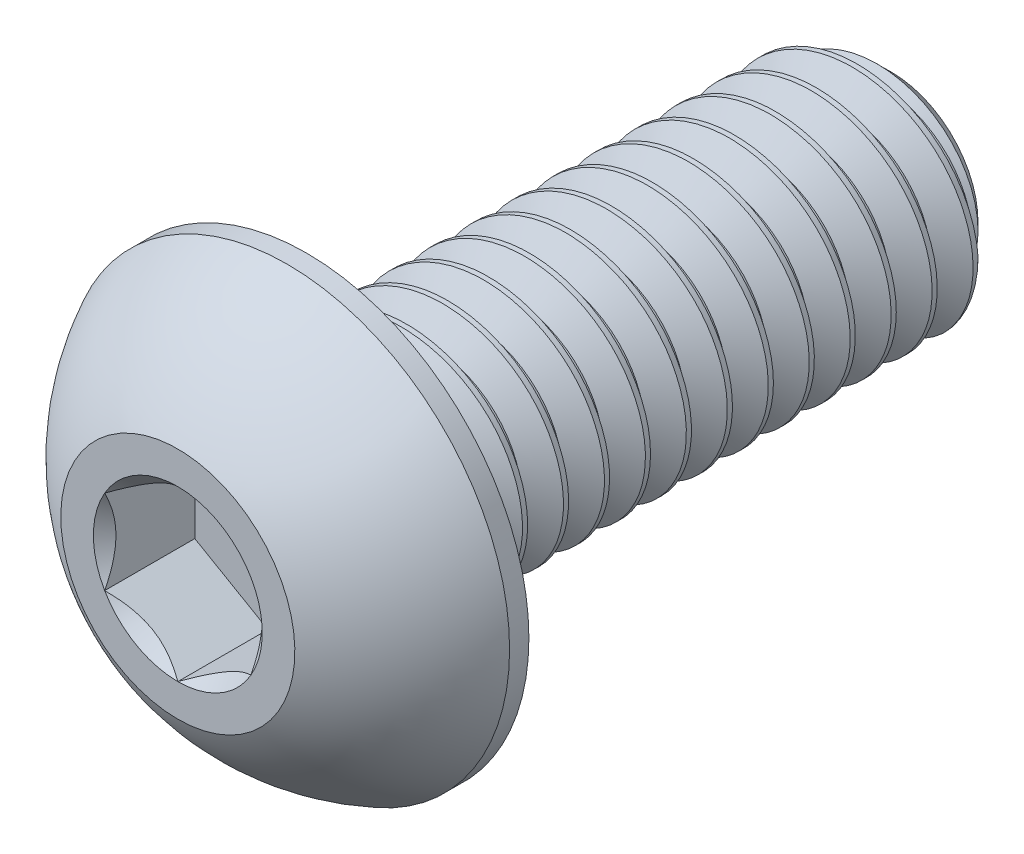
SolidWorks part; units mm, degrees
ref_plane "Front" through (0, 0, 0) normal (0, 0, 1) x (1, 0, 0)
ref_plane "Top" through (0, 0, 0) normal (0, 1, 0) x (1, 0, 0)
ref_plane "Right" through (0, 0, 0) normal (1, 0, 0) x (0, 0, -1)
sketch "Sketch1" plane through (0, 0, 0) normal (1, 0, 0) x (0, 0, -1)
  line L2 (2.2, 2) -> (12.2, 2)
  line L3 (12.2, 2) -> (12.2, 0)
  line L4 (12.2, 0) -> (2.2, 0)
  line L6 (1.87, 3.8) -> (2.2, 3.8) construction
  line L7 (12.2, 2) -> (12.2, -2) construction
  line L8 (0, 0) -> (2.2, 0) construction
  line L9 (2.2, 3.8) -> (2.2, -3.8) construction
  line L11 (2.2, 2) -> (2.2, 0)
  line L13 (0, 1.25) -> (0, -1.25) construction
  line L14 (0, 1.25) -> (0, 2) construction
  arc A3 (0, 2) -> (1.87, 3.8) centre (3.7264, 0) cw construction
  dimension "D1" = 0.33
revolve "Revolve1" add sketch "Sketch1" angle 360 mid plane about L4
sketch "Sketch3" plane through (0, 0, -12.2) normal (0, 0, -1) x (-1, 0, 0)
  circle A0 centre (0, 0) radius 2
curve "Helix/Spiral1" pitch 0.7 height 10.7 radius 2 centre (0, 0, -12.2) axis (0, 0, 1) start towards (0, 1, 0)
sketch "Sketch2" plane through (0, 0, 0) normal (1, 0, 0) x (0, 0, -1)
  line L0 (12.2, 2) -> (12.8125, 2)
  line L1 (12.8125, 2) -> (12.55, 1.5453)
  line L2 (12.55, 1.5453) -> (12.4625, 1.5453)
  line L3 (12.4625, 1.5453) -> (12.2, 2)
  line L4 (12.3312, 1.7727) -> (12.6812, 1.7727) construction
  dimension "D1" = 60
  dimension "D2" = 0.0875
  dimension "D3" = 0.35
chamfer "Chamfer1" distance 0.525 angle 45 1 edges at (0, 2, -12.2)
sweep "Cut-Sweep1" cut profiles "Sketch2" path "Helix/Spiral1" align with end faces yes
sketch "Sketch7" plane through (0, 0, 0) normal (1, 0, 0) x (0, 0, -1)
  line L6 (1.87, 3.8) -> (2.2, 3.8) construction
  line L8 (0, 0) -> (2.2, 0) construction
  line L11 (2.2, 3.8) -> (2.2, -3.8) construction
  line L12 (1.87, 3.8) -> (2.2, 3.8)
  line L13 (0, 0) -> (2.2, 0)
  line L14 (0, 1.25) -> (0, -1.25) construction
  line L15 (2.2, 3.8) -> (2.2, 0)
  line L16 (0, 2) -> (0, 0)
  arc A2 (1.87, 3.8) -> (0, 2) centre (3.7264, 0) ccw construction
  arc A3 (1.87, 3.8) -> (0, 2) centre (3.7264, 0) ccw
revolve "Revolve2" add sketch "Sketch7" angle 360 mid plane about L13
sketch "Sketch5" plane through (0, 0, 0) normal (0, 0, 1) x (1, 0, 0)
  line L1 (1.25, -0.7217) -> (1.25, 0.7217)
  line L2 (1.25, 0.7217) -> (0, 1.4434)
  line L3 (0, 1.4434) -> (-1.25, 0.7217)
  line L4 (-1.25, 0.7217) -> (-1.25, -0.7217)
  line L5 (-1.25, -0.7217) -> (0, -1.4434)
  line L6 (0, -1.4434) -> (1.25, -0.7217)
  circle A0 centre (0, 0) radius 1.25 construction
extrude "Cut-Extrude2" cut sketch "Sketch5" against normal blind 1.54
sketch "Sketch6" plane through (0, 0, 0) normal (0, 0, 1) x (1, 0, 0)
  circle A0 centre (0, 0) radius 1.4434
extrude "Cut-Extrude3" cut sketch "Sketch6" against normal blind 1.54 draft 45
sketch "Sketch9" [suppressed] plane through (0, 0, -2.2) normal (0, 0, 1) x (1, 0, 0)
  circle A2 centre (0, 0) radius 2
extrude "Boss-Extrude2" [suppressed] add sketch "Sketch9" against normal offset from surface (5 mm away) 28.575 up to face at (0, 1.475, -12.2)
sketch "Sketch10" plane through (0, 0, 0) normal (1, 0, 0) x (0, 0, -1)
  line L0 (12.2, 2) -> (12.2, -2) construction
  point P0 (11.15, -2)
  dimension "D1" = 1.05
equation "\"D3@Helix/Spiral1\" = \"Lg@Sketch1\" + \"D4@Helix/Spiral1\""
equation "\"D2@Sketch2\" = \"D4@Helix/Spiral1\" * .125"
equation "\"D3@Sketch2\" = \"D4@Helix/Spiral1\" * .5"
equation "\"D1@Chamfer1\" = \"D4@Helix/Spiral1\" * .75"
equation "\"D1@Cut-Extrude2\" = \"Head Ht@Sketch1\" * .7"
equation "\"D1@Sketch1\" = \"Head Ht@Sketch1\" * .15"
equation "\"D1@Sketch10\" = \"D4@Helix/Spiral1\" * 1.5"
equation "\"D1@Cut-Extrude3\" = \"D1@Cut-Extrude2\""
